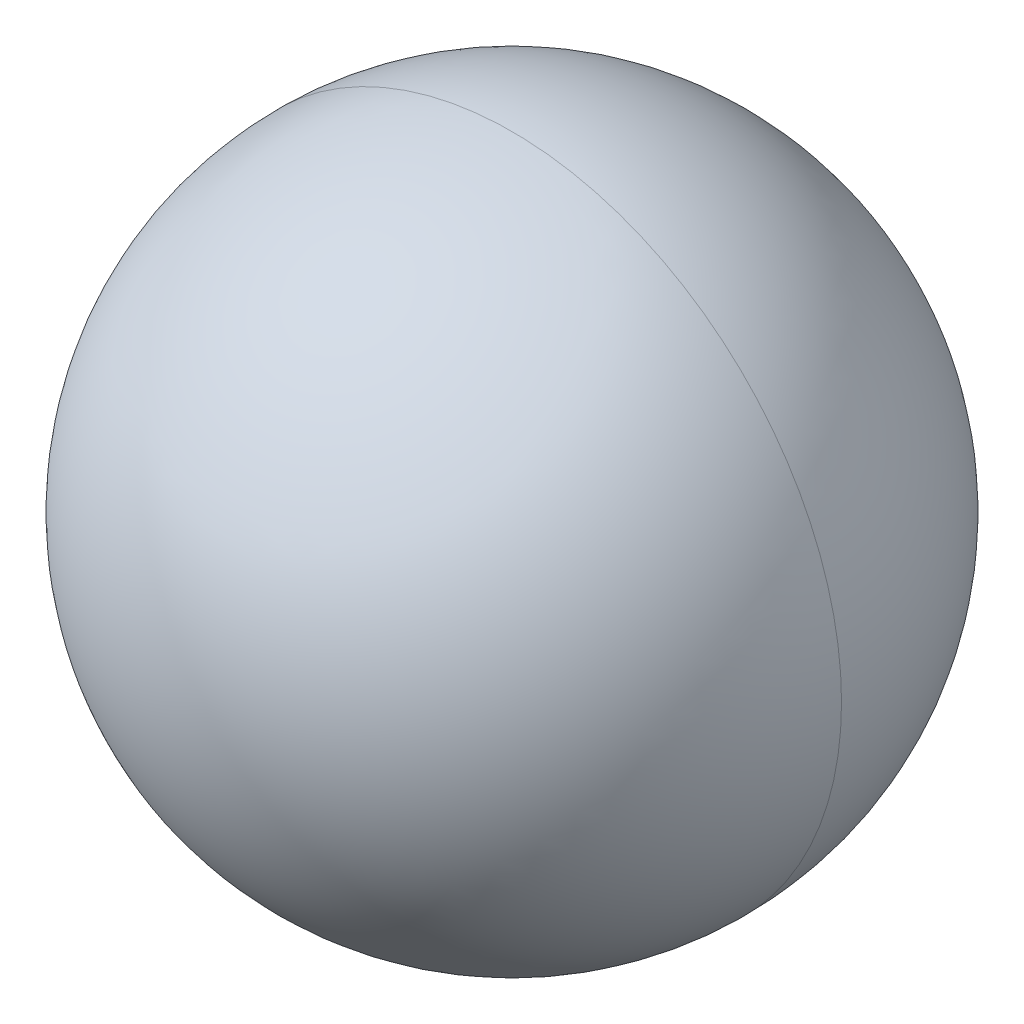
SolidWorks part; units mm, degrees
ref_plane "Front Plane" through (0, 0, 0) normal (0, 0, 1) x (1, 0, 0)
ref_plane "Top Plane" through (0, 0, 0) normal (0, 1, 0) x (1, 0, 0)
ref_plane "Right Plane" through (0, 0, 0) normal (1, 0, 0) x (0, 0, -1)
sketch "Sketch1" plane through (0, 0, 0) normal (0, 0, 1) x (1, 0, 0)
  circle A0 centre (0, 0) radius 12.5
  dimension "D1" = 25
extrude "Boss-Extrude1" add sketch "Sketch1" along normal blind 25
fillet "Fillet1" radius 12.5 2 edges at (12.5, 0, 0) (12.5, 0, 25)
